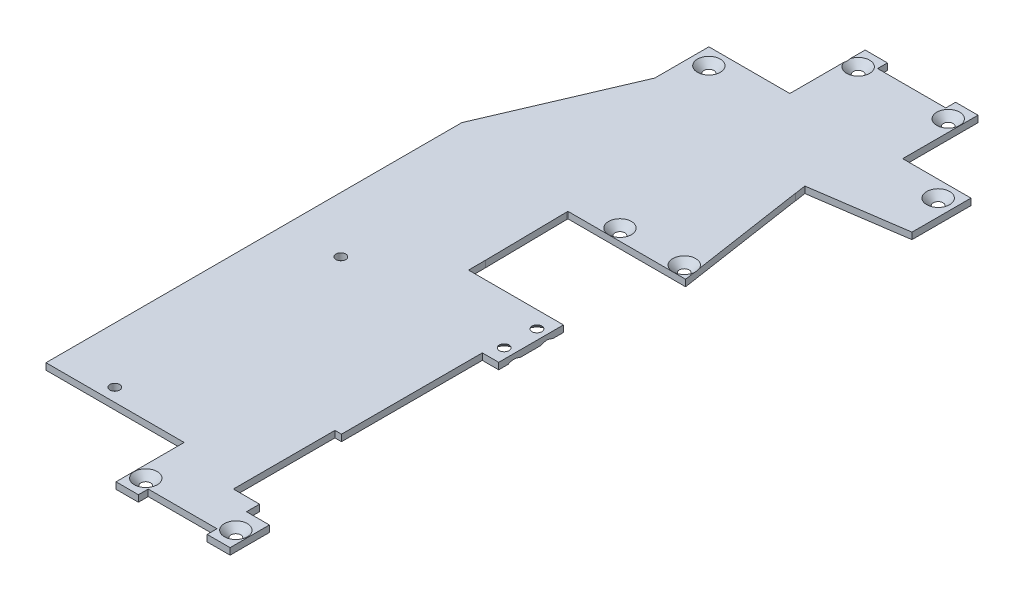
SolidWorks part; units mm, degrees
material "1060 Alloy"
ref_plane "Front Plane" through (0, 0, 0) normal (0, 0, 1) x (1, 0, 0)
ref_plane "Top Plane" through (0, 0, 0) normal (0, 1, 0) x (1, 0, 0)
ref_plane "Right Plane" through (0, 0, 0) normal (1, 0, 0) x (0, 0, -1)
sketch "Sketch1" plane through (0, 0, 0) normal (0, 1, 0) x (1, 0, 0)
  line L0 (0, 0) -> (0, 4.6042)
  line L1 (0, 4.6042) -> (7, 4.6042)
  line L2 (7, 4.6042) -> (7, 1.6042)
  line L3 (7, 1.6042) -> (27, 1.6042)
  line L4 (27, 1.6042) -> (27, 4.6042)
  line L5 (27, 4.6042) -> (34, 4.6042)
  line L6 (34, 4.6042) -> (34, -18.3958)
  line L7 (34, -18.3958) -> (52, -18.3958)
  line L8 (52, -18.3958) -> (52, -36.3958)
  line L9 (52, -36.3958) -> (23.9339, -43.8958)
  line L10 (23.9339, -43.8958) -> (29.9767, -83.8958)
  line L32 (-28, -34.9292) -> (-28, -18.3958)
  line L33 (-28, -18.3958) -> (0, -18.3958)
  line L34 (0, -18.3958) -> (0, 4.6042)
  line L41 (-5.6675, -91.8934) -> (-6.0233, -83.8958)
  line L42 (-6.0233, -83.8958) -> (29.9767, -83.8958)
  line L43 (-45.6675, -203.0967) -> (-45.6675, -76.1293)
  line L44 (-45.6675, -203.0967) -> (-2.6675, -203.0967)
  line L45 (-2.6675, -203.0967) -> (-2.6675, -223.8958)
  line L46 (-2.6675, -223.8958) -> (4.3325, -223.8958)
  line L47 (4.3325, -223.8958) -> (4.3325, -220.8958)
  line L48 (4.3325, -220.8958) -> (24.3325, -220.8958)
  line L49 (24.3325, -220.8958) -> (24.3325, -223.8958)
  line L50 (24.3325, -223.8958) -> (31.3325, -223.8958)
  line L51 (31.3325, -223.8958) -> (31.3325, -211.8958)
  line L52 (31.3325, -211.8958) -> (24.3325, -211.8958)
  line L53 (24.3325, -211.8958) -> (24.3325, -207.8958)
  line L54 (24.3325, -207.8958) -> (16.3325, -207.8958)
  line L55 (16.3325, -207.8958) -> (16.3325, -176.8958)
  line L56 (16.3325, -176.8958) -> (18.3325, -176.8958)
  line L57 (18.3325, -176.8958) -> (18.3325, -133.8958)
  line L58 (18.3325, -133.8958) -> (23.3325, -133.8958)
  line L59 (23.3325, -133.8958) -> (23.3325, -108.8958)
  line L60 (23.3325, -108.8958) -> (-5.6675, -108.8958)
  line L61 (-5.6675, -108.8958) -> (-6.0233, -83.8958)
  line L62 (-45.6675, -76.1293) -> (-28, -34.9292)
  circle A2 centre (47, -23.3958) radius 1.5
  circle A3 centre (-23, -23.3958) radius 1.5
  circle A4 centre (25.9767, -79.8958) radius 1.5
  circle A5 centre (6.3567, -79.8958) radius 1.5
  dimension "D33" = 3
  dimension "D34" = 3
  dimension "D37" = 3
  dimension "D39" = 3
  dimension "D1" = 3
  dimension "D2" = 20
  dimension "D3" = 34
  dimension "D4" = 23
  dimension "D5" = 23
  dimension "D6" = 18
  dimension "D7" = 28
  dimension "D8" = 18
  dimension "D9" = 25
  dimension "D10" = 40
  dimension "D11" = 29
  dimension "D12" = 25
  dimension "D13" = 5
  dimension "D14" = 43
  dimension "D15" = 2
  dimension "D16" = 31
  dimension "D17" = 36
  dimension "D18" = 8
  dimension "D19" = 4
  dimension "D20" = 7
  dimension "D21" = 20
  dimension "D22" = 34
  dimension "D23" = 43
  dimension "D24" = 3
  dimension "D25" = 3
  dimension "D26" = 12
  dimension "D30" = 5
  dimension "D31" = 5
  dimension "D32" = 5
  dimension "D35" = 4
  dimension "D36" = 4
  dimension "D38" = 19.62
  dimension "D43" = 7.5
extrude "Boss-Extrude1" add sketch "Sketch1" along normal blind 2 contours L60 L61 L42 L10 L9 L8 L7 L6 L5 L4 L3 L2 L1 L0 L34 L33 L32 L44 L45 L46 L47 L48 L49 L50 L51 L52 L53 L54 L55 L56 L57 L58 L59 A5 A4 A3 A2 region at (-6.643, 0, 107.6851)
sketch "Sketch2" plane through (0, 2, 0) normal (0, 1, 0) x (1, 0, 0)
  line L0 (23.3325, -133.8958) -> (23.3325, -108.8958) construction
  line L1 (-5.6675, -108.8958) -> (23.3325, -108.8958)
  line L2 (-5.6675, -108.8958) -> (-5.6675, -114.1232)
  line L3 (-5.6675, -114.1232) -> (23.3325, -114.1232)
  line L4 (23.3325, -108.8958) -> (23.3325, -114.1232)
chamfer "Chamfer1" distance 2 angle 45 4 edges at (-23, 2, 24.8958) (47, 2, 24.8958) (6.3567, 2, 81.3958) (25.9767, 2, 81.3958)
sketch "Sketch4" plane through (0, 2, 0) normal (0, 1, 0) x (1, 0, 0)
  line L1 (-6.0233, -83.8958) -> (30.2798, -83.8958)
  line L2 (-6.0233, -83.8958) -> (-6.0233, -83.4096)
  line L3 (-6.0233, -83.4096) -> (30.2798, -83.4096)
  line L4 (30.2798, -83.8958) -> (30.2798, -83.4096)
extrude "Cut-Extrude3" cut sketch "Sketch4" against normal blind 10
sketch "Sketch5" plane through (0, 2, 0) normal (0, 1, 0) x (1, 0, 0)
  line L0 (23.3325, -133.8958) -> (23.3325, -108.8958) construction
  line L1 (-5.6675, -108.8958) -> (23.3325, -108.8958)
  line L2 (-5.6675, -108.8958) -> (-5.6675, -110.2486)
  line L3 (-5.6675, -110.2486) -> (23.3325, -110.2486)
  line L4 (23.3325, -108.8958) -> (23.3325, -110.2486)
extrude "Cut-Extrude4" cut sketch "Sketch5" against normal blind 10
sketch "Sketch6" plane through (0, 2, 0) normal (0, 1, 0) x (1, 0, 0)
  circle A0 centre (-28.6675, -130.0967) radius 1.5
  circle A1 centre (-28.6675, -199.0967) radius 1.5
  dimension "D1" = 3
extrude "Cut-Extrude5" cut sketch "Sketch6" against normal blind 2
extrude "Cut-Extrude1" cut sketch "Sketch2" against normal blind 10
sketch "Sketch7" plane through (0, 2, 0) normal (0, 1, 0) x (1, 0, 0)
  circle A0 centre (20.3325, -119.2139) radius 1.5
  circle A1 centre (20.3325, -129.2139) radius 1.5
  dimension "D1" = 3
  dimension "D2" = 3
extrude "Cut-Extrude6" cut sketch "Sketch7" against normal blind 2
chamfer "Chamfer2" distance 2 angle 45 2 edges at (20.3325, 0, 120.7139) (20.3325, 0, 130.7139)
sketch "Sketch8" plane through (0, 2, 0) normal (0, 1, 0) x (1, 0, 0)
  line L0 (52, -36.3958) -> (22.949, -40.6261)
  line L2 (29.9033, -83.4096) -> (23.4592, -40.5518)
  line L3 (23.9339, -43.8958) -> (52, -36.3958)
  line L4 (23.9339, -43.8958) -> (23.4592, -40.5518)
  line M12 (23.9339, -43.8958) -> (52, -36.3958)
extrude "Cut-Extrude7" cut sketch "Sketch8" against normal blind 10 contours L2 L0 M12 region at (33.14, 2, 40.2787)
sketch "Sketch9" plane through (0, 2, 0) normal (0, 1, 0) x (1, 0, 0)
  line L1 (34, 4.6042) -> (31.155, 4.6042)
  line L2 (34, 4.6042) -> (34, 1.6042)
  line L3 (34, 1.6042) -> (31.155, 1.6042)
  line L4 (31.155, 4.6042) -> (31.155, 1.6042)
extrude "Cut-Extrude8" cut sketch "Sketch9" against normal blind 2
sketch "Sketch10" plane through (0, 2, 0) normal (0, 1, 0) x (1, 0, 0)
  line L1 (27, 1.6042) -> (24.3212, 1.6042)
  line L2 (27, 1.6042) -> (27, 4.6043)
  line L3 (27, 4.6043) -> (24.3212, 4.6043)
  line L4 (24.3212, 1.6042) -> (24.3212, 4.6043)
extrude "Boss-Extrude2" add sketch "Sketch10" against normal blind 2
sketch "Sketch11" plane through (0, 2, 0) normal (0, 1, 0) x (1, 0, 0)
  line L0 (0, 4.6042) -> (7, 4.6042) construction
  line L1 (7, 1.6042) -> (3.5, 1.6042)
  line L2 (7, 1.6042) -> (7, 4.6042)
  line L3 (7, 4.6042) -> (3.5, 4.6042)
  line L4 (3.5, 1.6042) -> (3.5, 4.6042)
extrude "Cut-Extrude9" cut sketch "Sketch11" against normal blind 2
sketch "Sketch12" plane through (0, 2, 0) normal (0, 1, 0) x (1, 0, 0)
  line L0 (-6.6788, 4.6043) -> (3.3212, 4.6043) construction
  line L1 (0, -18.3958) -> (-3.3, -18.3958)
  line L2 (0, -18.3958) -> (0, 4.6043)
  line L3 (0, 4.6043) -> (-3.3, 4.6043)
  line L4 (-3.3, -18.3958) -> (-3.3, 4.6043)
  dimension "D1" = 3.3
extrude "Boss-Extrude3" add sketch "Sketch12" against normal blind 2
sketch "Sketch13" plane through (0, 2, 0) normal (0, 1, 0) x (1, 0, 0)
  line L1 (31.155, 1.6042) -> (34, 1.6042)
  line L2 (31.155, 1.6042) -> (31.155, -18.3958)
  line L3 (31.155, -18.3958) -> (34, -18.3958)
  line L4 (34, 1.6042) -> (34, -18.3958)
extrude "Cut-Extrude10" cut sketch "Sketch13" against normal blind 2
sketch "Sketch14" plane through (0, 0, 0) normal (0, -1, 0) x (1, 0, 0)
  circle A0 centre (0.0712, 0.8957) radius 1.5
  circle A1 centre (27.5712, 0.8957) radius 1.5
extrude "Cut-Extrude11" cut sketch "Sketch14" against normal blind 2
chamfer "Chamfer3" distance 2 angle 45 2 edges at (27.5712, 2, -0.6043) (0.0712, 2, -0.6043)
sketch "Sketch15" plane through (0, 2, 0) normal (0, 1, 0) x (1, 0, 0)
  line L0 (-2.6675, -223.8958) -> (4.3325, -223.8958) construction
  line L1 (4.3325, -220.8958) -> (3.3406, -220.8958)
  line L2 (4.3325, -220.8958) -> (4.3325, -223.8958)
  line L3 (4.3325, -223.8958) -> (3.3406, -223.8958)
  line L4 (3.3406, -220.8958) -> (3.3406, -223.8958)
  line L5 (3.3406, -243.8954) -> (3.3406, -223.8954) construction
extrude "Cut-Extrude12" cut sketch "Sketch15" against normal blind 2
sketch "Sketch16" plane through (0, 2, 0) normal (0, 1, 0) x (1, 0, 0)
  line L0 (-45.6675, -203.0967) -> (-2.6675, -203.0967) construction
  line L1 (-2.6675, -223.8958) -> (-3.4938, -223.8958)
  line L2 (-2.6675, -223.8958) -> (-2.6675, -203.0967)
  line L3 (-2.6675, -203.0967) -> (-3.4938, -203.0967)
  line L4 (-3.4938, -223.8958) -> (-3.4938, -203.0967)
extrude "Boss-Extrude4" add sketch "Sketch16" against normal blind 2
sketch "Sketch17" plane through (0, 0, 0) normal (0, -1, 0) x (1, 0, 0)
  circle A0 centre (27.5906, 218.3954) radius 1.5
  circle A1 centre (0.0906, 218.3954) radius 1.5
extrude "Cut-Extrude13" cut sketch "Sketch17" against normal blind 2
chamfer "Chamfer4" distance 2 angle 45 2 edges at (0.0906, 2, 216.8954) (27.5906, 2, 216.8954)
